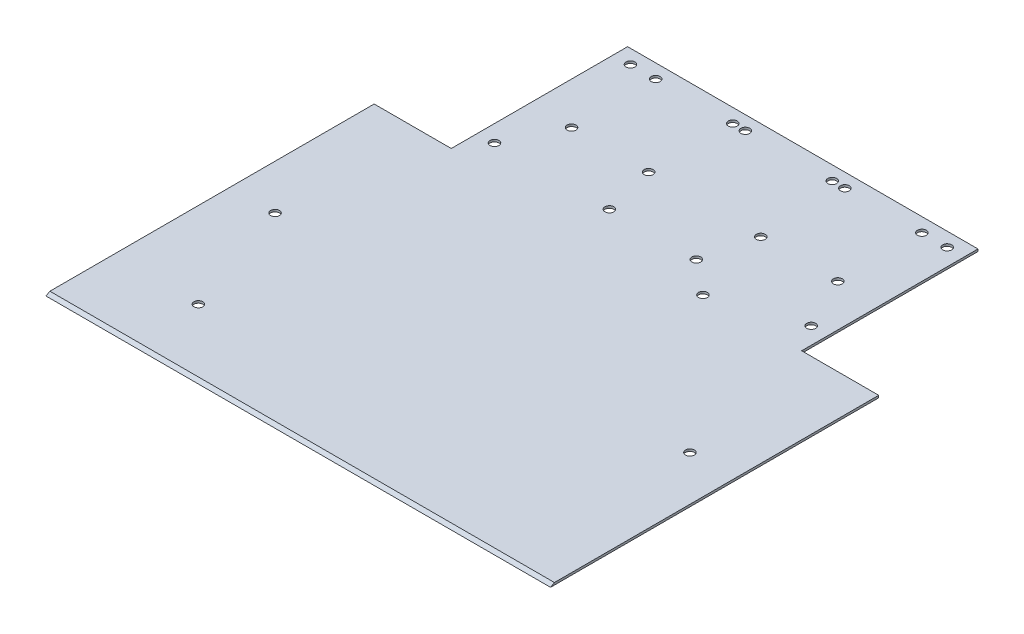
SolidWorks part; units mm, degrees
ref_plane "Alzado" through (0, 0, 0) normal (0, 0, 1) x (1, 0, 0)
ref_plane "Planta" through (0, 0, 0) normal (0, 1, 0) x (1, 0, 0)
ref_plane "Vista lateral" through (0, 0, 0) normal (1, 0, 0) x (0, 0, -1)
sketch "Croquis1" plane through (0, 0, 0) normal (0, 1, 0) x (1, 0, 0)
  line L0 (-62.5, 90) -> (-62.5, 27.08)
  line L1 (90, -90) -> (-90, -90)
  line L2 (90, -90) -> (90, 27.08)
  line L3 (62.5, 90) -> (-62.5, 90)
  line L4 (-90, -90) -> (-90, 27.08)
  line L5 (90, -90) -> (-62.5, 62.5) construction
  line L6 (62.5, 62.5) -> (-90, -90) construction
  line L7 (-62.5, 27.08) -> (-90, 27.08)
  line L8 (0, 90) -> (0, -90) construction
  line L9 (62.5, 27.08) -> (90, 27.08)
  line L10 (62.5, 90) -> (62.5, 27.08)
  point P0 (0, 0)
  dimension "D1" = 125
  dimension "D2" = 180
  dimension "D3" = 27.5
  dimension "D4" = 62.92
  dimension "D5" = 27.5
extrude "Saliente-Extruir1" add sketch "Croquis1" along normal blind 0.8
sketch "Croquis2" plane through (-90, 0, 0) normal (-1, 0, 0) x (0, 0, 1)
  line L0 (90, 0) -> (88.6144, 0.8)
  line L1 (-27.08, 0.8) -> (90, 0.8) construction
  line L2 (88.6144, 0.8) -> (90, 0.8)
  line L3 (90, 0.8) -> (90, 0)
  dimension "D1" = 60
extrude "Cortar-Extruir1" cut sketch "Croquis2" against normal up to next
sketch "Croquis3" plane through (0, 0.8, 0) normal (0, 1, 0) x (1, 0, 0)
  circle A0 centre (74, -24.2793) radius 1.585
extrude "Cortar-Extruir2" cut sketch "Croquis3" against normal up to next
mirror "Simetría1" about plane through (0, 0, 0) normal (1, 0, 0) of "Cortar-Extruir2"
sketch "Croquis4" plane through (0, 0.8, 0) normal (0, 1, 0) x (1, 0, 0)
  circle A0 centre (-56.5, 36.5056) radius 1.585
  circle A1 centre (-15.5, 36.5056) radius 1.585
  circle A2 centre (-15.5, 85.0056) radius 1.585
  circle A3 centre (-56.5, 85.0056) radius 1.585
extrude "Cortar-Extruir3" cut sketch "Croquis4" against normal up to next
sketch "Croquis6" plane through (0, 0.8, 0) normal (0, 1, 0) x (1, 0, 0)
  circle A0 centre (56.5, 85.0056) radius 1.585
  circle A1 centre (15.5, 85.0056) radius 1.585
  circle A2 centre (15.5, 36.5056) radius 1.585
  circle A3 centre (56.5, 36.5056) radius 1.585
extrude "Cortar-Extruir4" cut sketch "Croquis6" against normal up to next
sketch "Croquis7" plane through (0, 0.8, 0) normal (0, 1, 0) x (1, 0, 0)
  circle A0 centre (-20, 85.0056) radius 1.585
  circle A1 centre (-47.5, 85.0056) radius 1.585
  circle A2 centre (-47.5, 55.0056) radius 1.585
  circle A3 centre (-20, 55.0056) radius 1.585
extrude "Cortar-Extruir5" cut sketch "Croquis7" against normal up to next
mirror "Simetría2" about plane through (0, 0, 0) normal (1, 0, 0) of "Cortar-Extruir5"
sketch "Croquis8" plane through (0, 0.8, 0) normal (0, 1, 0) x (1, 0, 0)
  circle A0 centre (-59.4792, -66.1418) radius 1.585
  circle A1 centre (27.6408, 26.7382) radius 1.585
extrude "Cortar-Extruir6" cut sketch "Croquis8" against normal up to next
